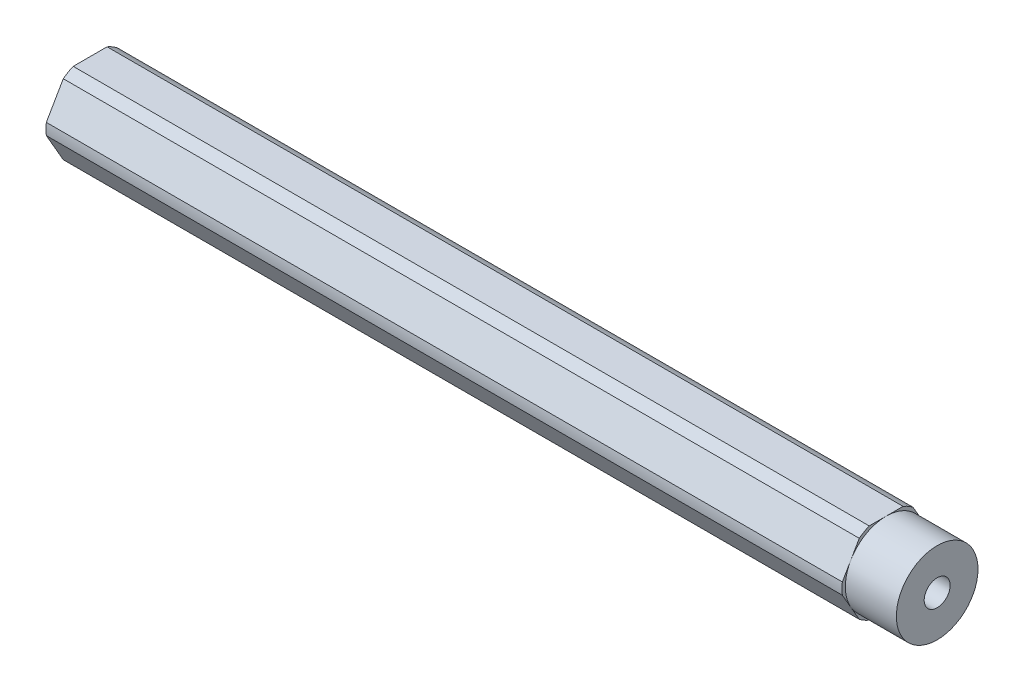
SolidWorks part; units mm, degrees
material "7075-T6 (SN)"
ref_plane "Front Plane" through (0, 0, 0) normal (0, 0, 1) x (1, 0, 0)
ref_plane "Top Plane" through (0, 0, 0) normal (0, 1, 0) x (1, 0, 0)
ref_plane "Right Plane" through (0, 0, 0) normal (1, 0, 0) x (0, 0, -1)
sketch "Sketch1" plane through (0, 0, 0) normal (1, 0, 0) x (0, 0, -1)
  line L1 (3.6662, 6.35) -> (-3.6662, 6.35)
  line L2 (-3.6662, 6.35) -> (-7.3323, 0)
  line L3 (-7.3323, 0) -> (-3.6662, -6.35)
  line L4 (-3.6662, -6.35) -> (3.6662, -6.35)
  line L5 (3.6662, -6.35) -> (7.3323, 0)
  line L6 (7.3323, 0) -> (3.6662, 6.35)
  circle A0 centre (0, 0) radius 6.875
  circle A1 centre (0, 0) radius 2.0193
  circle A2 centre (0, 0) radius 6.35 construction
  dimension "D1" = 12.7
  dimension "D2" = 13.75
  dimension "D3" = 4.0386
extrude "Boss-Extrude1" add sketch "Sketch1" along normal mid plane 131.7625 contours L6 A0 L1 L2 L3 L4 L5 A1 region at (0, 5.7918, -3.3439)
hole_wizard "#10-32 Tapped Hole1" positions "3DSketch1" profile "Sketch2" tap size "#10-32" standard "ANSI Inch"
sketch3d "3DSketch1"
  circle A0 centre (-65.8813, 0, 0) radius 2.0193 construction
  circle A1 centre (65.8813, 0, 0) radius 2.0193 construction
  point P0 (65.8813, 0, 0)
  point P2 (-65.8813, 0, 0)
  point P7 (-63.862, 0, 0)
  point P10 (67.9006, 0, 0)
sketch "Sketch2" plane through (65.8813, 0, 0) normal (0, 1, 0) x (0, 0, -1)
  line L0 (0, 0) -> (0, 17.5608)
  line L1 (0, 17.5608) -> (2.0193, 16.3474)
  line L2 (2.0193, 16.3474) -> (2.0193, 0)
  line L5 (2.0193, 0) -> (0, 0)
  line L10 (0, 17.5608) -> (-2.0193, 16.3474) construction
  line L11 (0, -6.35) -> (0, 107.95) construction
  dimension "Tap Drill Dia." = 4.0386
  dimension "Tap Drill Depth" = 16.3474
  dimension "Drill Angle" = 118
cosmetic thread "Hole Thread1" parameters "D1"=13.97, "D2"=4.826
cosmetic thread "Hole Thread2" parameters "D1"=13.97, "D2"=4.826
sketch "Sketch3" plane through (65.8813, 0, 0) normal (1, 0, 0) x (0, 0, -1)
  circle A0 centre (0, 0) radius 6.35
  dimension "D1" = 12.7
extrude "Cut-Extrude-Thin1" cut sketch "Sketch3" against normal blind 7.9375 thin thin type one direction wall 2.54
equation "\"D2@Sketch1\"=13.75mm"
